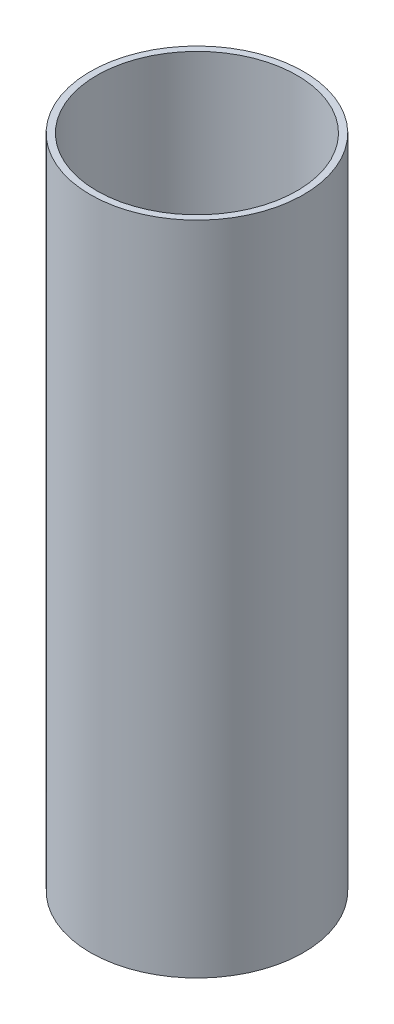
SolidWorks part; units mm, degrees
ref_plane "Front Plane" through (0, 0, 0) normal (0, 0, 1) x (1, 0, 0)
ref_plane "Top Plane" through (0, 0, 0) normal (0, 1, 0) x (1, 0, 0)
ref_plane "Right Plane" through (0, 0, 0) normal (1, 0, 0) x (0, 0, -1)
sketch "Sketch1" plane through (0, 0, 0) normal (0, 1, 0) x (1, 0, 0)
  circle A0 centre (0, 0) radius 30.5
  circle A1 centre (0, 0) radius 32.5
extrude "Boss-Extrude1" add sketch "Sketch1" along normal blind 200
